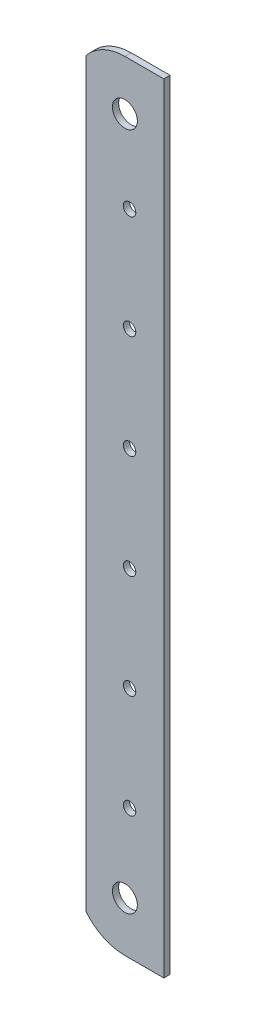
SolidWorks part; units mm, degrees
ref_plane "Front Plane" through (0, 0, 0) normal (0, 0, 1) x (1, 0, 0)
ref_plane "Top Plane" through (0, 0, 0) normal (0, 1, 0) x (1, 0, 0)
ref_plane "Right Plane" through (0, 0, 0) normal (1, 0, 0) x (0, 0, -1)
sketch "Sketch1" plane through (0, 0, 0) normal (0, 0, 1) x (1, 0, 0)
  line L0 (-12.5, 0) -> (12.5, 0) construction
  line L1 (3.5, 125) -> (12.5, 125)
  line L2 (-12.5, 109) -> (-12.5, -109)
  line L3 (3.5, -125) -> (12.5, -125)
  line L4 (12.5, 125) -> (12.5, -125)
  line L5 (-12.5, 125) -> (12.5, -125) construction
  line L6 (-12.5, -125) -> (12.5, 125) construction
  line L7 (-12.5, 109) -> (-12.5, 125) construction
  line L8 (-12.5, 125) -> (3.5, 125) construction
  line L9 (-12.5, 109) -> (-12.5, 125) construction
  line L10 (-12.5, 109) -> (-12.5, 118.9875)
  line L11 (3.5, 125) -> (0, 125)
  line L12 (3.5, -125) -> (0, -125)
  line L13 (-12.5, -109) -> (-12.5, -118.9875)
  circle A0 centre (0, 109) radius 4
  circle A1 centre (0, -109) radius 4
  arc A4 (0, 125) -> (-12.5, 118.9875) centre (0, 109) ccw
  arc A5 (-12.5, -118.9875) -> (0, -125) centre (0, -109) ccw
  point P0 (0, 0)
  dimension "D4" = 8
  dimension "D5" = 32
  dimension "D7" = 32
  dimension "D1" = 25
  dimension "D3" = 218
  dimension "D6" = 250
extrude "Boss-Extrude1" add sketch "Sketch1" along normal blind 2
sketch "Sketch2" plane through (0, 0, 2) normal (0, 0, 1) x (1, 0, 0)
  circle A0 centre (1.5, 83.3) radius 2
  circle A1 centre (1.5, 50) radius 2
  circle A2 centre (1.5, 16.7) radius 2
  circle A3 centre (1.5, -16.7) radius 2
  circle A4 centre (1.5, -50) radius 2
  circle A5 centre (1.5, -83.3) radius 2
extrude "Cut-Extrude1" cut sketch "Sketch2" against normal blind 2
